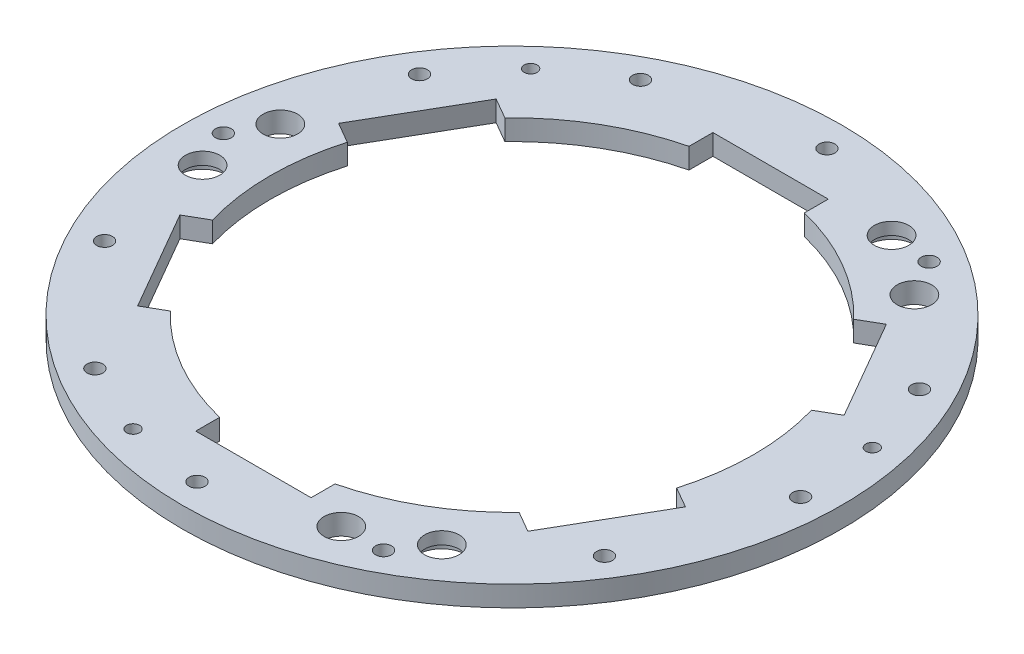
SolidWorks part; units mm, degrees
material "6061 Alloy"
ref_plane "Front Plane" through (0, 0, 0) normal (0, 0, 1) x (1, 0, 0)
ref_plane "Top Plane" through (0, 0, 0) normal (0, 1, 0) x (1, 0, 0)
ref_plane "Right Plane" through (0, 0, 0) normal (1, 0, 0) x (0, 0, -1)
sketch "Sketch1" plane through (0, 0, 0) normal (0, 1, 0) x (1, 0, 0)
  line L0 (-13.335, -54.2656) -> (-13.335, -58.1814)
  line L1 (13.335, -54.2656) -> (13.335, -58.1814)
  line L2 (-13.335, -59.7901) -> (13.335, -59.7901)
  line L3 (13.335, -58.1814) -> (13.335, -59.7901)
  line L4 (-13.335, -58.1814) -> (-13.335, -59.7901)
  line L5 (0, 0) -> (-65.7887, -5.7558) construction
  line L6 (0, 0) -> (-3.0468, -69.7835) construction
  line L7 (0, 0) -> (0, -26.4169) construction
  line L8 (0, 0) -> (-21.0043, -66.6171) construction
  line L9 (-65.0367, 11.4677) -> (0, 0) construction
  circle A0 centre (0, 0) radius 55.88
  circle A1 centre (0, 0) radius 76.2
  circle A2 centre (0, 0) radius 59.69
  circle A3 centre (-3.0468, -69.7835) radius 1.8288
  circle A4 centre (-65.7887, -5.7558) radius 3.9903
  circle A5 centre (-65.0367, 11.4677) radius 3.9903
  circle A6 centre (-21.0043, -66.6171) radius 1.5
  point P24 (0, 0)
  point P29 (0, 0)
  dimension "D1" = 111.76
  dimension "D2" = 152.4
  dimension "D8" = 3.6576
  dimension "D11" = 7.9807
  dimension "D12" = 7.9807
  dimension "D16" = 3
  dimension "D4" = 13.335
  dimension "D5" = 13.335
  dimension "D7" = 69.85
  dimension "D6" = 5.5245
  dimension "D9" = 66.04
  dimension "D10" = 82.5
  dimension "D15" = 15
  dimension "D13" = 2.5
  dimension "D14" = 15
  dimension "D3" = 3.81
extrude "Boss-Extrude1" add sketch "Sketch1" along normal blind 4.7625 contours L1 A2 L0 A0 | A1 A2 A0 region at (-15.0127, 0, 56.2235) region at (-74.0447, 0, 0)
pattern_circular "CirPattern1" count 6 over 360 about axis through (0, 4.7625, 0) along (0, 1, 0) of face at (-13.335, 2.3813, 57.0278) of face at (13.335, 2.3813, 57.0278) of face at (0, 2.3813, 59.7901)
pattern_circular "CirPattern7" count 12 over 360 about axis through (0, 4.7625, 0) along (0, 1, 0) of face at (-3.0468, 4.7625, 71.6123)
sketch "Sketch4" plane through (0, 0, 0) normal (0, -1, 0) x (1, 0, 0)
  line L0 (0, 0) -> (-65.7887, 5.7558) construction
  line L1 (0, 0) -> (0, -39.7137) construction
  circle A0 centre (-65.7887, 5.7558) radius 5.588
  circle A2 centre (-65.7887, 5.7558) radius 3.9903 construction
  circle A3 centre (-65.7887, 5.7558) radius 3.9903
  point P12 (0, 0)
  dimension "D2" = 11.176
extrude "Cut-Extrude1" cut sketch "Sketch4" against normal blind 1.905 contours A0 region at (-71.2186, 0, 5.7558)
pattern_circular "CirPattern2" count 3 over 360 about axis through (0, 0, 0) along (0, 1, 0) of face at (-65.7887, 4.7625, 9.7461) of face at (-65.7887, 1.905, 1.7654) of face at (-65.7887, 1.905, 0.1678) of face at (-65.0367, 4.7625, -7.4774) of face at (-21.0043, 4.7625, 68.1171)
sketch "Sketch5" plane through (0, 4.7625, 0) normal (0, 1, 0) x (1, 0, 0)
  line L0 (0, 0) -> (-20.0894, -55.1952)
  line L1 (0, 0) -> (0, -18.6852)
  line L2 (-16.5968, -53.0258) -> (-18.2257, -57.5011) construction
  line L3 (-18.2257, -57.5011) -> (-22.9993, -55.7636) construction
  line L4 (-22.9993, -55.7636) -> (-21.3704, -51.2884) construction
  line L5 (-59.7924, -7.9638) -> (-55.1022, -7.1368)
  line L6 (-54.2201, -12.1397) -> (-58.9103, -12.9667)
  line L7 (-58.9103, -12.9667) -> (-59.7924, -7.9638)
  line L8 (-36.7931, 47.7998) -> (-33.7318, 44.1515)
  line L9 (-37.6233, 40.8862) -> (-40.6846, 44.5345)
  line L10 (-40.6846, 44.5345) -> (-36.7931, 47.7998)
  line L11 (22.9993, 55.7636) -> (21.3704, 51.2884)
  line L12 (16.5968, 53.0258) -> (18.2257, 57.5011)
  line L13 (18.2257, 57.5011) -> (22.9993, 55.7636)
  line L14 (59.7924, 7.9638) -> (55.1022, 7.1368)
  line L15 (54.2201, 12.1397) -> (58.9103, 12.9667)
  line L16 (58.9103, 12.9667) -> (59.7924, 7.9638)
  line L17 (36.7931, -47.7998) -> (33.7318, -44.1515)
  line L18 (37.6233, -40.8862) -> (40.6846, -44.5345)
  line L19 (40.6846, -44.5345) -> (36.7931, -47.7998)
  circle A0 centre (0, 0) radius 55.5625
  circle A1 centre (0, 0) radius 58.7375 construction
  circle A2 centre (0, 0) radius 55.5625
  circle A3 centre (0, 0) radius 55.5625
  circle A4 centre (0, 0) radius 55.5625
  circle A5 centre (0, 0) radius 55.5625
  circle A6 centre (0, 0) radius 55.5625
  circle A7 centre (0, 0) radius 76.2
  circle A8 centre (0, 0) radius 63.5
  point P38 (0, 0)
  dimension "D1" = 111.125
  dimension "D3" = 20
  dimension "D4" = 2.54
  dimension "D5" = 4.7625
  dimension "D6" = 2.54
  dimension "D2" = 3.175
  dimension "D8" = 12.7
  dimension "D7" = 6
split line "Split Line1" [suppressed]
equation "\"Middle Coupler Inner Daimeter\"= 3.875in"
equation "\"Middle Coupler  Wall Thickness\" = 0.25in"
equation "\"Middle Coupler Bottom Thickness\"= 0.2in"
equation "\"Bearing Rail Offset\"= 0.45in"
equation "\"3-56 UNF Tap\"= 0.089in"
equation "\"3-56 UNF Clearance\"= 0.104in"
equation "\"Ball Bearing Distance\"= 0.03in"
equation "\"D1@Sketch1\"=\"Middle Coupler Inner Daimeter\"+0.5+0.0125*2in"
equation "\"TCA Outer Diameter\" = 6in"
equation "\"D2@Sketch1\"=\"TCA Outer Diameter\""
equation "\"D4@Sketch1\"=0.50 + (0.05/2)"
equation "\"D5@Sketch1\"=\"D4@Sketch1\""
equation "\"D7@Sketch1\"=(\"D2@Sketch1\"-0.5)/2"
equation "\"D8@Sketch1\"=\"6-32 Clearance\""
equation "\"Interstage Aeroframe Wall Thickness\" = 0.072in"
equation "\"Compression Spring OD\"= 0.42in"
equation "\"10-24 Tap\"= 0.1495in"
equation "\"10-24 Clearance\"= 0.196in"
equation "\"D2@Sketch4\"=\"Compression Spring OD\"+0.02"
equation "\"D3@Sketch1\"=0.125in+(0.05/2)"
equation "\"Lower Stage Fuselage Wall Thickness\" = 0.25in"
equation "\"6-32 Tap\" = 0.107in"
equation "\"1/4-20 Tap\" = 0.201in"
equation "\"3-48 Tap\"= 0.079in"
equation "\"12-24 Tap\" = 0.177in"
equation "\"3-48 Clearance\" = 0.104in"
equation "\"6-32 Clearance\" = 0.144in"
equation "\"D6@Sketch1\"=3/16 + 0.03"
equation "\"D9@Sketch1\"=(\"D2@Sketch1\"+\"D1@Sketch1\")/4+0.1-.1"
equation "\"D1@Sketch5\"=\"Middle Coupler Inner Daimeter\"+0.5"
equation "\"D5@Sketch5\"=3/16"
equation "\"D6@Sketch5\"=\"D4@Sketch5\""
equation "\"D1@Boss-Extrude1\"=3/16"
equation "\"4-40 Tap\"= 0.089in"
equation "\"4-40 Clearance\" = 0.116in"
equation "\"12-24 Major Diameter\"= 0.216in"
equation "\"D16@Sketch1\"=3mm"
equation "\"D11@Sketch1\"=\"D12@Sketch1\""
